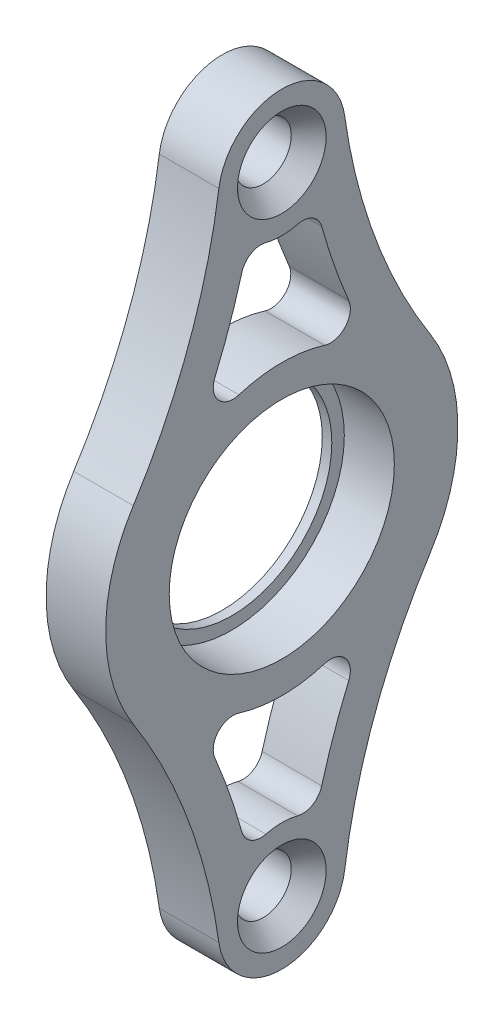
SolidWorks part; units mm, degrees
material "6061-T6 (SS)"
ref_plane "Front Plane" through (0, 0, 0) normal (0, 0, 1) x (1, 0, 0)
ref_plane "Top Plane" through (0, 0, 0) normal (0, 1, 0) x (1, 0, 0)
ref_plane "Right Plane" through (0, 0, 0) normal (1, 0, 0) x (0, 0, -1)
ref_plane "Plane1" through (54.442, 0, 0) normal (-1, 0, 0) x (0, 0, 1)
sketch "Sketch1" plane through (54.442, 0, 0) normal (-1, 0, 0) x (0, 0, 1)
  line L0 (-51.1134, 32.5835) -> (-5.0306, 26.107) construction
  line L1 (-23.0873, 0) -> (0, 0) construction
  line L2 (0, 0) -> (0, 25.4) construction
  circle A0 centre (0, -25.4) radius 2.2479 construction
  circle A1 centre (0, 25.4) radius 2.2479 construction
  circle A2 centre (0, -25.4) radius 2.2479
  circle A3 centre (0, 25.4) radius 2.2479
  circle A4 centre (0, 0) radius 9
  circle A5 centre (0, 0) radius 6 construction
  arc A6 (-11.8728, 7.5686) -> (-11.8728, -7.5686) centre (0, 0) ccw
  arc A7 (5.0306, 26.107) -> (-5.0306, 26.107) centre (0, 25.4) ccw
  arc A8 (-5.0306, -26.107) -> (5.0306, -26.107) centre (0, -25.4) ccw
  arc A9 (-5.0306, 26.107) -> (-11.8728, 7.5686) centre (-51.1134, 32.5835) cw
  arc A10 (5.0306, 26.107) -> (11.8728, 7.5686) centre (51.1134, 32.5835) ccw
  arc A11 (5.0306, -26.107) -> (11.8728, -7.5686) centre (51.1134, -32.5835) cw
  arc A12 (-5.0306, -26.107) -> (-11.8728, -7.5686) centre (-51.1134, -32.5835) ccw
  arc A13 (11.8728, -7.5686) -> (11.8728, 7.5686) centre (0, 0) ccw
  dimension "D1" = 18
  dimension "D2" = 12
  dimension "D4" = 10.16
  dimension "D3" = 5.08
  dimension "D5" = 8
extrude "Boss-Extrude1" add sketch "Sketch1" along normal blind 4.7625
sketch "Sketch2" plane through (49.6795, 0, 0) normal (-1, 0, 0) x (0, 0, 1)
  arc A0 (-9.1955, 5.8619) -> (-1.8865, 25.6651) centre (-51.1134, 32.5835) ccw
  arc A1 (1.8865, 25.6651) -> (-1.8865, 25.6651) centre (0, 25.4) ccw
  arc A2 (1.8865, 25.6651) -> (9.1955, 5.8619) centre (51.1134, 32.5835) ccw
  arc A3 (9.1955, -5.8619) -> (9.1955, 5.8619) centre (0, 0) ccw
  arc A4 (9.1955, -5.8619) -> (1.8865, -25.6651) centre (51.1134, -32.5835) ccw
  arc A5 (-1.8865, -25.6651) -> (1.8865, -25.6651) centre (0, -25.4) ccw
  arc A6 (-1.8865, -25.6651) -> (-9.1955, -5.8619) centre (-51.1134, -32.5835) ccw
  arc A7 (-9.1955, 5.8619) -> (-9.1955, -5.8619) centre (0, 0) ccw
  arc A8 (-11.8728, 7.5686) -> (-5.0306, 26.107) centre (-51.1134, 32.5835) ccw
  arc A9 (-11.8728, 7.5686) -> (-11.8728, -7.5686) centre (0, 0) ccw
  arc A10 (-5.0306, -26.107) -> (-11.8728, -7.5686) centre (-51.1134, -32.5835) ccw
  arc A11 (-5.0306, -26.107) -> (5.0306, -26.107) centre (0, -25.4) ccw
  arc A12 (11.8728, -7.5686) -> (5.0306, -26.107) centre (51.1134, -32.5835) ccw
  arc A13 (11.8728, -7.5686) -> (11.8728, 7.5686) centre (0, 0) ccw
  arc A14 (5.0306, 26.107) -> (11.8728, 7.5686) centre (51.1134, 32.5835) ccw
  arc A15 (5.0306, 26.107) -> (-5.0306, 26.107) centre (0, 25.4) ccw
  arc A16 (-11.8728, 7.5686) -> (-5.0306, 26.107) centre (-51.1134, 32.5835) ccw construction
  arc A17 (-11.8728, 7.5686) -> (-11.8728, -7.5686) centre (0, 0) ccw construction
  arc A18 (-5.0306, -26.107) -> (-11.8728, -7.5686) centre (-51.1134, -32.5835) ccw construction
  arc A19 (-5.0306, -26.107) -> (5.0306, -26.107) centre (0, -25.4) ccw construction
  arc A20 (11.8728, -7.5686) -> (5.0306, -26.107) centre (51.1134, -32.5835) ccw construction
  arc A21 (11.8728, -7.5686) -> (11.8728, 7.5686) centre (0, 0) ccw construction
  arc A22 (5.0306, 26.107) -> (11.8728, 7.5686) centre (51.1134, 32.5835) ccw construction
  arc A23 (5.0306, 26.107) -> (-5.0306, 26.107) centre (0, 25.4) ccw construction
  circle A24 centre (0, 0) radius 11.54
  circle A25 centre (0, 25.4) radius 5.08
  circle A26 centre (0, -25.4) radius 5.08
  circle A27 centre (0, 0) radius 9 construction
  dimension "D3" = 2.54
  dimension "D1" = 0
  dimension "D2" = 3.175
extrude "Cut-Extrude1" cut sketch "Sketch2" against normal through all contours A25 A0 A24 A2 | A26 A4 A24 A6 region at (49.6795, 15.0199, 0) region at (49.6795, -15.0199, 0)
fillet "Fillet1" radius 1.5875 8 edges at (52.0607, 8.8063, 7.4579) (52.0607, 8.8063, -7.4579) (52.0607, 21.1234, 2.7417) (52.0607, -8.8063, -7.4579) (52.0607, -8.8063, 7.4579) (52.0607, -21.1234, 2.7417) (52.0607, -21.1234, -2.7417) (52.0607, 21.1234, -2.7417)
sketch "Sketch5" plane through (54.442, 0, 0) normal (-1, 0, 0) x (0, 0, 1)
  point P0 (0, 25.4)
  point P3 (0, -25.4)
hole_wizard "CSK for #6 Flat Head Machine Screw1" positions "Sketch5" profile "Sketch4" countersink size "#6" standard "ANSI Inch"
sketch "Sketch4" plane through (54.442, 25.4, 0) normal (0, 1, 0) x (0, 0, -1)
  line L0 (0, 0) -> (0, 7.6434)
  line L1 (0, 7.6434) -> (2.1526, 6.35)
  line L2 (2.1526, 6.35) -> (2.1526, 1.5998)
  line L3 (2.1526, 1.5998) -> (3.5433, 0)
  line L5 (3.5433, 0) -> (0, 0)
  line L6 (-2.1526, 1.5998) -> (-3.5433, 0) construction
  line L10 (0, 7.6434) -> (-2.1526, 6.35) construction
  line L11 (0, -6.35) -> (0, 107.95) construction
  dimension "Hole Dia." = 4.3053
  dimension "Hole Depth" = 6.35
  dimension "Near C'Sink Dia." = 7.0866
  dimension "Near C'Sink Angle" = 82
  dimension "Drill Angle" = 118
sketch "Sketch6" plane through (54.442, 0, 0) normal (1, 0, 0) x (0, 0, -1)
  circle A0 centre (0, 0) radius 9 construction
  circle A1 centre (0, 0) radius 9
  circle A2 centre (0, 0) radius 8
  dimension "D1" = 1
extrude "Boss-Extrude2" add sketch "Sketch6" along normal offset from surface (0.7625 mm away) 4 from surface up to face at (54.442, 25.4, -3.5433) starting at face at (49.6795, -15.9859, 0)
equation "\"D1@Sketch1\"=18mm"
equation "\"D2@Sketch1\"=12mm"
equation "\"D1@Boss-Extrude2\"=4mm"
